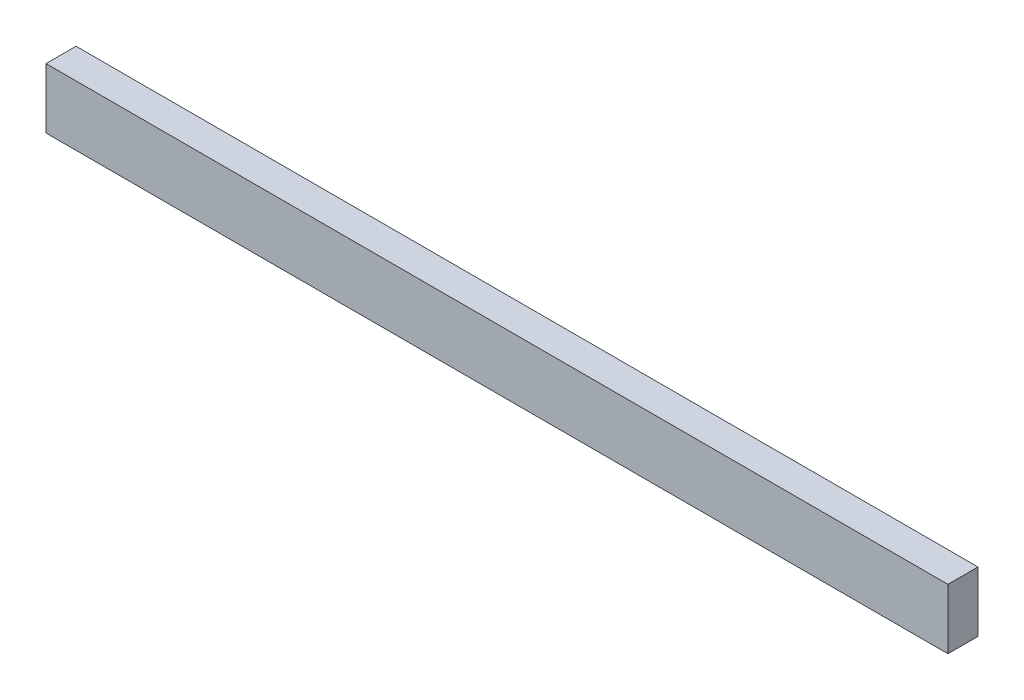
SolidWorks part; units mm, degrees
material "Cast Alloy Steel"
ref_plane "Front Plane" through (0, 0, 0) normal (0, 0, 1) x (1, 0, 0)
ref_plane "Top Plane" through (0, 0, 0) normal (0, 1, 0) x (1, 0, 0)
ref_plane "Right Plane" through (0, 0, 0) normal (1, 0, 0) x (0, 0, -1)
sketch "Sketch1" plane through (0, 0, 0) normal (0, 0, 1) x (1, 0, 0)
  line L1 (0, 0) -> (3000, 0)
  line L2 (0, 0) -> (0, -200)
  line L3 (0, -200) -> (3000, -200)
  line L4 (3000, 0) -> (3000, -200)
  dimension "D1" = 3000
  dimension "D2" = 200
extrude "Boss-Extrude1" add sketch "Sketch1" along normal blind 100
